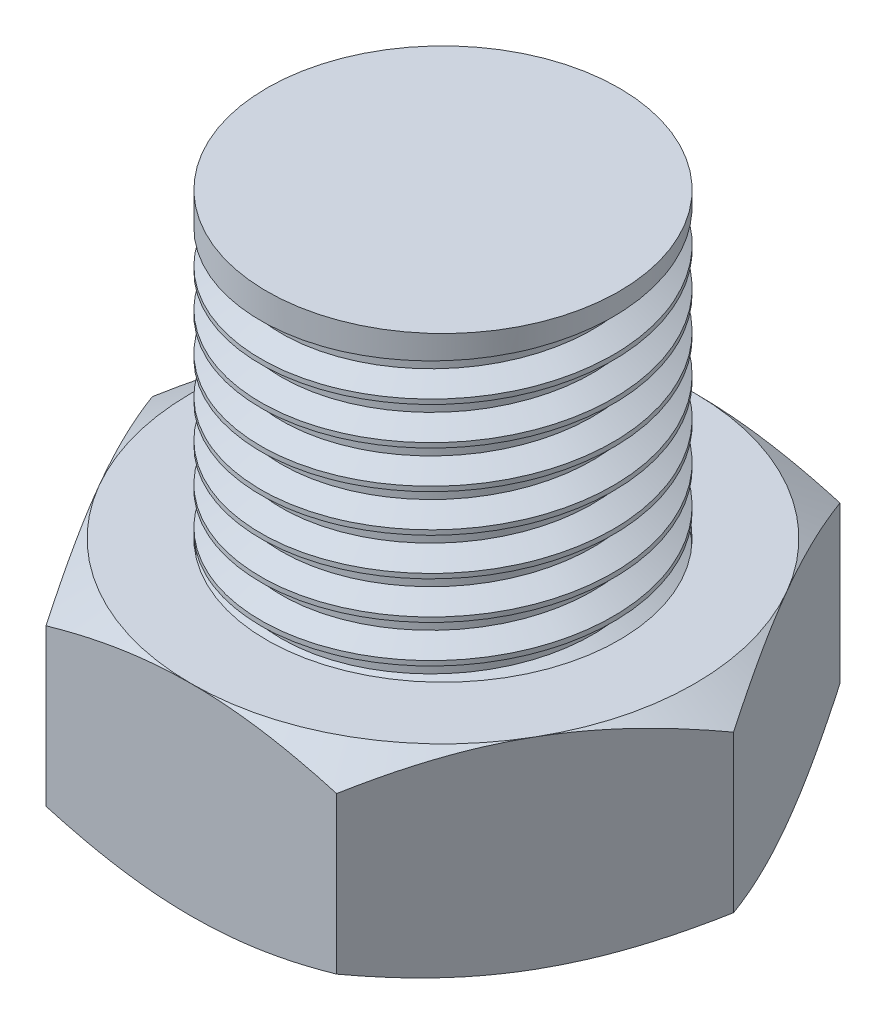
SolidWorks part; units mm, degrees
ref_plane "前视基准面" through (0, 0, 0) normal (0, 0, 1) x (1, 0, 0)
ref_plane "上视基准面" through (0, 0, 0) normal (0, 1, 0) x (1, 0, 0)
ref_plane "右视基准面" through (0, 0, 0) normal (1, 0, 0) x (0, 0, -1)
sketch "草图1" plane through (0, 0, 0) normal (0, 1, 0) x (1, 0, 0)
  line L1 (11.547, 0) -> (5.7735, 10)
  line L2 (5.7735, 10) -> (-5.7735, 10)
  line L3 (-5.7735, 10) -> (-11.547, 0)
  line L4 (-11.547, 0) -> (-5.7735, -10)
  line L5 (-5.7735, -10) -> (5.7735, -10)
  line L6 (5.7735, -10) -> (11.547, 0)
  circle A0 centre (0, 0) radius 10 construction
  dimension "D1" = 20
extrude "凸台-拉伸1" add sketch "草图1" along normal blind 8
sketch "草图4" plane through (0, 0, 0) normal (0, 0, 1) x (1, 0, 0)
  line L0 (0, -1.5016) -> (0, 11.6214) construction
  line L1 (-11.547, 8) -> (-10, 8)
  line L2 (-11.547, 8) -> (-5.7735, 8) construction
  line L3 (-10, 8) -> (-11.547, 7.1068)
  line L4 (-11.547, 8) -> (-11.547, 0) construction
  line L5 (-11.547, 7.1068) -> (-11.547, 8)
  line L6 (-11.547, 0.8932) -> (-10, 0)
  line L7 (-11.547, 0) -> (-5.7735, 0) construction
  line L8 (-10, 0) -> (-11.547, 0)
  line L9 (-11.547, 0) -> (-11.547, 0.8932)
  dimension "D1" = 10
  dimension "D2" = 30
  dimension "D3" = 30
revolve "切除-旋转1" cut sketch "草图4" angle 360 about L0
sketch "草图5" plane through (0, 8, 0) normal (0, 1, 0) x (1, 0, 0)
  circle A0 centre (0, 0) radius 7
  dimension "D1" = 14
extrude "凸台-拉伸2" add sketch "草图5" along normal blind 12
thread "螺纹线1" pitch 1.5 method cut profile "螺纹线轮廓1" start angle 0, offset 0, length 12, pitch 1.5, diameter 14
ref_plane "基准面1" through (-7, 20, 0) normal (0, 0, 1) x (-1, 0, 0)
sketch "螺纹线轮廓1" plane through (-7, 20, 0) normal (0, 0, 1) x (-1, 0, 0)
  line L0 (0, 0) -> (0, 1.5) construction
  line L11 (0, 0) -> (0, 1.3125)
  line L12 (0, 1.3125) -> (-0.8119, 0.8437)
  line L13 (-0.8119, 0.8437) -> (-0.8119, 0.4687)
  line L15 (-0.8119, 0.4687) -> (0, 0)
  line L17 (-0.8119, 0.6562) -> (0, 0.6562) construction
  point P2 (0, 0)
  dimension "Pitch" = 1.5
  dimension "Profile_Angle" = 60
  dimension "Profile_Land" = 0.375
  dimension "Profile_Height" = 0.8119
chamfer "倒角1" distance 0.5 angle 45 1 edges at (-7, 19.3438, 0)
